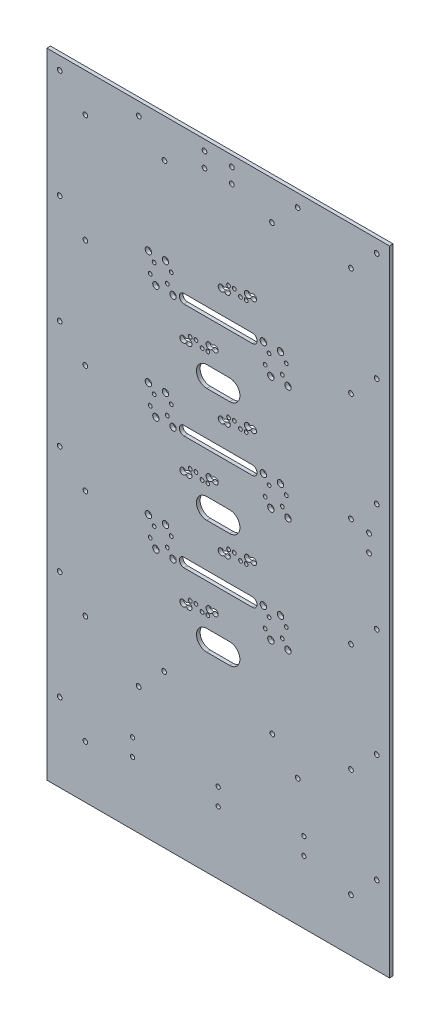
SolidWorks part; units mm, degrees
ref_plane "Front Plane" through (0, 0, 0) normal (0, 0, 1) x (1, 0, 0)
ref_plane "Top Plane" through (0, 0, 0) normal (0, 1, 0) x (1, 0, 0)
ref_plane "Right Plane" through (0, 0, 0) normal (1, 0, 0) x (0, 0, -1)
sketch "Sketch1" plane through (0, 0, 0) normal (0, 0, 1) x (1, 0, 0)
  line L0 (-165.9868, 389.7156) -> (134.0132, 389.7156) construction
  line L1 (-165.9868, 389.7156) -> (134.0132, 389.7156)
  line L2 (-165.9868, 389.7156) -> (-165.9868, -165.2844)
  line L3 (-165.9868, -165.2844) -> (134.0132, -165.2844)
  line L4 (134.0132, 389.7156) -> (134.0132, -165.2844)
  line L5 (89.0132, -165.2844) -> (134.0132, -165.2844) construction
  line L6 (134.0132, 389.7156) -> (134.0132, -165.2844) construction
  dimension "D2" = 300
extrude "Boss-Extrude1" add sketch "Sketch1" along normal blind 3.175
sketch "Sketch2" plane through (0, 0, 0) normal (0, 0, -1) x (-1, 0, 0)
  line L0 (15.9868, -165.2844) -> (15.9868, 389.7156) construction
  line L1 (165.9868, -165.2844) -> (-134.0132, -165.2844) construction
  line L2 (-134.0132, 389.7156) -> (165.9868, 389.7156) construction
  line L3 (0.9868, 59.7156) -> (30.9868, 59.7156) construction
  line L4 (0.9868, 159.7156) -> (30.9868, 159.7156) construction
  line L5 (0.9868, 259.7156) -> (30.9868, 259.7156) construction
  point P8 (15.9868, 59.7156)
  point P11 (15.9868, 159.7156)
  dimension "D1" = 30
  dimension "D2" = 30
  dimension "D3" = 100
  dimension "D4" = 100
  dimension "D5" = 130
sketch "Sketch4" plane through (0, 0, 3.175) normal (0, 0, 1) x (1, 0, 0)
  line L0 (-45.9868, 259.7156) -> (14.0132, 259.7156) construction
  line L1 (-45.9868, 263.7156) -> (14.0132, 263.7156)
  line L2 (-45.9868, 255.7156) -> (14.0132, 255.7156)
  line L3 (-15.9868, -165.2844) -> (-15.9868, 389.7156) construction
  line L4 (-0.9868, 259.7156) -> (-30.9868, 259.7156) construction
  line L5 (-45.9868, 159.7156) -> (14.0132, 159.7156) construction
  line L6 (-45.9868, 163.7156) -> (14.0132, 163.7156)
  line L7 (-45.9868, 155.7156) -> (14.0132, 155.7156)
  line L8 (-45.9868, 59.7156) -> (14.0132, 59.7156) construction
  line L9 (-45.9868, 63.7156) -> (14.0132, 63.7156)
  line L10 (-45.9868, 55.7156) -> (14.0132, 55.7156)
  line L11 (-0.9868, 59.7156) -> (-30.9868, 59.7156) construction
  line L12 (-0.9868, 159.7156) -> (-30.9868, 159.7156) construction
  arc A0 (-45.9868, 263.7156) -> (-45.9868, 255.7156) centre (-45.9868, 259.7156) ccw
  arc A1 (14.0132, 255.7156) -> (14.0132, 263.7156) centre (14.0132, 259.7156) ccw
  arc A2 (-45.9868, 163.7156) -> (-45.9868, 155.7156) centre (-45.9868, 159.7156) ccw
  arc A3 (14.0132, 155.7156) -> (14.0132, 163.7156) centre (14.0132, 159.7156) ccw
  arc A4 (-45.9868, 63.7156) -> (-45.9868, 55.7156) centre (-45.9868, 59.7156) ccw
  arc A5 (14.0132, 55.7156) -> (14.0132, 63.7156) centre (14.0132, 59.7156) ccw
  point P2 (-15.9868, 259.7156)
  point P14 (-15.9868, 159.7156)
  point P21 (-15.9868, 59.7156)
  dimension "D1" = 15
  dimension "D2" = 8
  dimension "D3" = 15
  dimension "D4" = 8
  dimension "D5" = 15
  dimension "D6" = 8
extrude "Cut-Extrude1" cut sketch "Sketch4" against normal blind 10
sketch "Sketch5" plane through (0, 0, 0) normal (0, 0, -1) x (-1, 0, 0)
  line L0 (45.9868, 155.7156) -> (-14.0132, 155.7156) construction
sketch "Sketch6" plane through (0, 0, 0) normal (0, 0, -1) x (-1, 0, 0)
  line L0 (-134.0132, 389.7156) -> (165.9868, 389.7156) construction
  circle A0 centre (3.9868, 380.7156) radius 2.05
  circle A1 centre (27.9868, 380.7156) radius 2.05
  circle A2 centre (27.9868, 367.7156) radius 2.05
  circle A3 centre (3.9868, 367.7156) radius 2.05
  point P12 (42.9868, 389.7156)
  point P13 (0, 0)
  point P16 (0, 0)
  point P17 (0, 0)
  point P18 (0, 0)
  point P21 (0, 0)
  dimension "D1" = 15
  dimension "D2" = 4.1
  dimension "D3" = 39
  dimension "D4" = 9
  dimension "D5" = 22
extrude "Cut-Extrude5" cut sketch "Sketch6" against normal blind 51
sketch "Sketch8" plane through (0, 0, 0) normal (0, 0, -1) x (-1, 0, 0)
  circle A0 centre (-116.0132, 162.9803) radius 2.1
  circle A1 centre (-116.0132, 147.9803) radius 2.1
  dimension "D1" = 4.2
extrude "Cut-Extrude7" cut sketch "Sketch8" against normal blind 67
sketch "Sketch9" plane through (0, 0, 0) normal (0, 0, -1) x (-1, 0, 0)
  line L0 (15.9868, 389.7156) -> (15.9868, 432.1874) construction
  line L1 (-134.0132, 389.7156) -> (165.9868, 389.7156) construction
  circle A0 centre (-122.7632, 378.4656) radius 2.05
  circle A1 centre (-100.2632, 355.9656) radius 2.05
  circle A2 centre (-53.5368, 378.4656) radius 2.05
  circle A3 centre (-31.0368, 355.9656) radius 2.05
  circle A4 centre (-122.7632, 283.4656) radius 2.05
  circle A5 centre (-100.2632, 260.9656) radius 2.05
  circle A6 centre (-122.7632, 188.4656) radius 2.05
  circle A7 centre (-100.2632, 165.9656) radius 2.05
  circle A8 centre (-122.7632, 93.4656) radius 2.05
  circle A9 centre (-100.2632, 70.9656) radius 2.05
  circle A10 centre (-122.7632, -1.5344) radius 2.05
  circle A11 centre (-100.2632, -24.0344) radius 2.05
  circle A12 centre (-122.7632, -96.5344) radius 2.05
  circle A13 centre (-100.2632, -119.0344) radius 2.05
  circle A14 centre (-122.7632, -191.5344) radius 2.05
  circle A15 centre (-100.2632, -214.0344) radius 2.05
  circle A16 centre (-53.6482, -54.0344) radius 2.05
  circle A17 centre (-31.371, -31.5344) radius 2.05
  circle A18 centre (63.3447, -31.5344) radius 2.05
  circle A19 centre (85.6219, -54.0344) radius 2.05
  circle A20 centre (132.2368, -214.0344) radius 2.05
  circle A21 centre (154.7368, -191.5344) radius 2.05
  circle A22 centre (132.2368, -119.0344) radius 2.05
  circle A23 centre (154.7368, -96.5344) radius 2.05
  circle A24 centre (132.2368, -24.0344) radius 2.05
  circle A25 centre (154.7368, -1.5344) radius 2.05
  circle A26 centre (132.2368, 70.9656) radius 2.05
  circle A27 centre (154.7368, 93.4656) radius 2.05
  circle A28 centre (132.2368, 165.9656) radius 2.05
  circle A29 centre (154.7368, 188.4656) radius 2.05
  circle A30 centre (132.2368, 260.9656) radius 2.05
  circle A31 centre (154.7368, 283.4656) radius 2.05
  circle A32 centre (63.0104, 355.9656) radius 2.05
  circle A33 centre (85.5104, 378.4656) radius 2.05
  circle A34 centre (132.2368, 355.9656) radius 2.05
  circle A35 centre (154.7368, 378.4656) radius 2.05
  dimension "D1" = 7
extrude "Cut-Extrude8" cut sketch "Sketch9" against normal blind 10
sketch "Sketch10" plane through (0, 0, 0) normal (0, 0, -1) x (-1, 0, 0)
  circle A0 centre (35.464, 33.6216) radius 1.651
  circle A1 centre (25.1051, 30.1602) radius 1.651
  arc A2 (43.5999, 30.6974) -> (43.5999, 26.4941) centre (41.7588, 28.5958) ccw
  arc A3 (20.6514, 37.2877) -> (20.6514, 33.0844) centre (18.8103, 35.186) ccw
  circle A4 centre (-30.1263, 38.9336) radius 2.794
  circle A5 centre (-23.5434, 61.8842) radius 2.794
  circle A6 centre (-25.1024, 45.23) radius 1.651
  circle A7 centre (-28.5672, 55.5878) radius 1.651
  circle A8 centre (-45.1263, 38.9336) radius 2.794
  circle A9 centre (-38.5434, 61.8842) radius 2.794
  circle A10 centre (-40.1024, 45.23) radius 1.651
  circle A11 centre (-43.5672, 55.5878) radius 1.651
  circle A12 centre (40.464, 33.6216) radius 1.651
  circle A13 centre (30.1051, 30.1602) radius 1.651
  arc A14 (44.9177, 26.4941) -> (44.9177, 30.6974) centre (46.7588, 28.5958) ccw
  arc A15 (21.9693, 33.0844) -> (21.9693, 37.2877) centre (23.8103, 35.186) ccw
  arc A16 (21.9693, 33.0844) -> (20.6514, 33.0844) centre (21.3103, 32.3322) ccw
  arc A17 (21.9693, 37.2877) -> (20.6514, 37.2877) centre (21.3103, 38.0399) cw
  arc A18 (44.9177, 26.4941) -> (43.5999, 26.4941) centre (44.2588, 25.7419) ccw
  arc A19 (44.9177, 30.6974) -> (43.5999, 30.6974) centre (44.2588, 31.4496) cw
  circle A40 centre (55.5171, 57.5469) radius 2.794
  circle A41 centre (70.5171, 57.5469) radius 2.794
  circle A42 centre (75.5409, 63.8433) radius 1.651
  circle A43 centre (60.5409, 63.8433) radius 1.651
  circle A44 centre (-3.4904, 85.8095) radius 1.651
  circle A45 centre (6.8686, 89.271) radius 1.651
  arc A46 (-11.6262, 88.7337) -> (-11.6262, 92.937) centre (-9.7851, 90.8353) ccw
  arc A47 (11.3223, 82.1435) -> (11.3223, 86.3468) centre (13.1633, 84.2451) ccw
  circle A48 centre (62.0999, 80.4975) radius 2.794
  circle A49 centre (57.0761, 74.2011) radius 1.651
  circle A50 centre (77.0999, 80.4975) radius 2.794
  circle A51 centre (72.0761, 74.2011) radius 1.651
  circle A52 centre (-8.4904, 85.8095) radius 1.651
  circle A53 centre (1.8686, 89.271) radius 1.651
  arc A54 (-12.9441, 92.937) -> (-12.9441, 88.7337) centre (-14.7851, 90.8353) ccw
  arc A55 (10.0044, 86.3468) -> (10.0044, 82.1435) centre (8.1633, 84.2451) ccw
  arc A56 (10.0044, 86.3468) -> (11.3223, 86.3468) centre (10.6633, 87.099) ccw
  arc A57 (10.0044, 82.1435) -> (11.3223, 82.1435) centre (10.6633, 81.3913) cw
  arc A58 (-12.9441, 92.937) -> (-11.6262, 92.937) centre (-12.2851, 93.6892) ccw
  arc A59 (-12.9441, 88.7337) -> (-11.6262, 88.7337) centre (-12.2851, 87.9815) cw
  circle A60 centre (63.0104, 355.9656) radius 2.05 construction
  circle A62 centre (35.464, 133.6216) radius 1.651
  circle A63 centre (25.1051, 130.1602) radius 1.651
  arc A64 (43.5999, 130.6974) -> (43.5999, 126.4941) centre (41.7588, 128.5958) ccw
  arc A65 (20.6514, 137.2877) -> (20.6514, 133.0844) centre (18.8103, 135.186) ccw
  circle A66 centre (-30.1263, 138.9336) radius 2.794
  circle A67 centre (-23.5434, 161.8842) radius 2.794
  circle A68 centre (-25.1024, 145.23) radius 1.651
  circle A69 centre (-28.5672, 155.5878) radius 1.651
  circle A70 centre (-45.1263, 138.9336) radius 2.794
  circle A71 centre (-38.5434, 161.8842) radius 2.794
  circle A72 centre (-40.1024, 145.23) radius 1.651
  circle A73 centre (-43.5672, 155.5878) radius 1.651
  circle A74 centre (40.464, 133.6216) radius 1.651
  circle A75 centre (30.1051, 130.1602) radius 1.651
  arc A76 (44.9177, 126.4941) -> (44.9177, 130.6974) centre (46.7588, 128.5958) ccw
  arc A77 (21.9693, 133.0844) -> (21.9693, 137.2877) centre (23.8103, 135.186) ccw
  arc A78 (21.9693, 133.0844) -> (20.6514, 133.0844) centre (21.3103, 132.3322) ccw
  arc A79 (21.9693, 137.2877) -> (20.6514, 137.2877) centre (21.3103, 138.0399) cw
  arc A80 (44.9177, 126.4941) -> (43.5999, 126.4941) centre (44.2588, 125.7419) ccw
  arc A81 (44.9177, 130.6974) -> (43.5999, 130.6974) centre (44.2588, 131.4496) cw
  circle A82 centre (55.5171, 157.5469) radius 2.794
  circle A83 centre (70.5171, 157.5469) radius 2.794
  circle A84 centre (75.5409, 163.8433) radius 1.651
  circle A85 centre (60.5409, 163.8433) radius 1.651
  circle A86 centre (-3.4904, 185.8095) radius 1.651
  circle A87 centre (6.8686, 189.271) radius 1.651
  arc A88 (-11.6262, 188.7337) -> (-11.6262, 192.937) centre (-9.7851, 190.8353) ccw
  arc A89 (11.3223, 182.1435) -> (11.3223, 186.3468) centre (13.1633, 184.2451) ccw
  circle A90 centre (62.0999, 180.4975) radius 2.794
  circle A91 centre (57.0761, 174.2011) radius 1.651
  circle A92 centre (77.0999, 180.4975) radius 2.794
  circle A93 centre (72.0761, 174.2011) radius 1.651
  circle A94 centre (-8.4904, 185.8095) radius 1.651
  circle A95 centre (1.8686, 189.271) radius 1.651
  arc A96 (-12.9441, 192.937) -> (-12.9441, 188.7337) centre (-14.7851, 190.8353) ccw
  arc A97 (10.0044, 186.3468) -> (10.0044, 182.1435) centre (8.1633, 184.2451) ccw
  arc A98 (10.0044, 186.3468) -> (11.3223, 186.3468) centre (10.6633, 187.099) ccw
  arc A99 (10.0044, 182.1435) -> (11.3223, 182.1435) centre (10.6633, 181.3913) cw
  arc A100 (-12.9441, 192.937) -> (-11.6262, 192.937) centre (-12.2851, 193.6892) ccw
  arc A101 (-12.9441, 188.7337) -> (-11.6262, 188.7337) centre (-12.2851, 187.9815) cw
  circle A102 centre (35.464, 233.6216) radius 1.651
  circle A103 centre (25.1051, 230.1602) radius 1.651
  arc A104 (43.5999, 230.6974) -> (43.5999, 226.4941) centre (41.7588, 228.5958) ccw
  arc A105 (20.6514, 237.2877) -> (20.6514, 233.0844) centre (18.8103, 235.186) ccw
  circle A106 centre (-30.1263, 238.9336) radius 2.794
  circle A107 centre (-23.5434, 261.8842) radius 2.794
  circle A108 centre (-25.1024, 245.23) radius 1.651
  circle A109 centre (-28.5672, 255.5878) radius 1.651
  circle A110 centre (-45.1263, 238.9336) radius 2.794
  circle A111 centre (-38.5434, 261.8842) radius 2.794
  circle A112 centre (-40.1024, 245.23) radius 1.651
  circle A113 centre (-43.5672, 255.5878) radius 1.651
  circle A114 centre (40.464, 233.6216) radius 1.651
  circle A115 centre (30.1051, 230.1602) radius 1.651
  arc A116 (44.9177, 226.4941) -> (44.9177, 230.6974) centre (46.7588, 228.5958) ccw
  arc A117 (21.9693, 233.0844) -> (21.9693, 237.2877) centre (23.8103, 235.186) ccw
  arc A118 (21.9693, 233.0844) -> (20.6514, 233.0844) centre (21.3103, 232.3322) ccw
  arc A119 (21.9693, 237.2877) -> (20.6514, 237.2877) centre (21.3103, 238.0399) cw
  arc A120 (44.9177, 226.4941) -> (43.5999, 226.4941) centre (44.2588, 225.7419) ccw
  arc A121 (44.9177, 230.6974) -> (43.5999, 230.6974) centre (44.2588, 231.4496) cw
  circle A122 centre (55.5171, 257.5469) radius 2.794
  circle A123 centre (70.5171, 257.5469) radius 2.794
  circle A124 centre (75.5409, 263.8433) radius 1.651
  circle A125 centre (60.5409, 263.8433) radius 1.651
  circle A126 centre (-3.4904, 285.8095) radius 1.651
  circle A127 centre (6.8686, 289.271) radius 1.651
  arc A128 (-11.6262, 288.7337) -> (-11.6262, 292.937) centre (-9.7851, 290.8353) ccw
  arc A129 (11.3223, 282.1435) -> (11.3223, 286.3468) centre (13.1633, 284.2451) ccw
  circle A130 centre (62.0999, 280.4975) radius 2.794
  circle A131 centre (57.0761, 274.2011) radius 1.651
  circle A132 centre (77.0999, 280.4975) radius 2.794
  circle A133 centre (72.0761, 274.2011) radius 1.651
  circle A134 centre (-8.4904, 285.8095) radius 1.651
  circle A135 centre (1.8686, 289.271) radius 1.651
  arc A136 (-12.9441, 292.937) -> (-12.9441, 288.7337) centre (-14.7851, 290.8353) ccw
  arc A137 (10.0044, 286.3468) -> (10.0044, 282.1435) centre (8.1633, 284.2451) ccw
  arc A138 (10.0044, 286.3468) -> (11.3223, 286.3468) centre (10.6633, 287.099) ccw
  arc A139 (10.0044, 282.1435) -> (11.3223, 282.1435) centre (10.6633, 281.3913) cw
  arc A140 (-12.9441, 292.937) -> (-11.6262, 292.937) centre (-12.2851, 293.6892) ccw
  arc A141 (-12.9441, 288.7337) -> (-11.6262, 288.7337) centre (-12.2851, 287.9815) cw
  dimension "D3" = 1
  dimension "D4" = 1
  dimension "D5" = 3
  dimension "D1" = 2
  dimension "D2" = 2
extrude "Cut-Extrude9" cut sketch "Sketch10" against normal blind 10
sketch "Sketch12" plane through (0, 0, 0) normal (0, 0, -1) x (-1, 0, 0)
  circle A0 centre (90.9868, -95.2078) radius 1.85
  circle A1 centre (90.9868, -110.2078) radius 1.85
  circle A2 centre (15.9868, -95.2078) radius 1.85
  circle A3 centre (15.9868, -110.2078) radius 1.85
  circle A4 centre (-59.0132, -95.2078) radius 1.85
  circle A5 centre (-59.0132, -110.2078) radius 1.85
  dimension "D1" = 3
extrude "Cut-Extrude10" cut sketch "Sketch12" against normal blind 10
sketch "Sketch13" plane through (0, 0, 3.175) normal (0, 0, 1) x (1, 0, 0)
  line L0 (-15.9868, 55.7156) -> (-15.9868, 10.7156) construction
  line L1 (-45.9868, 55.7156) -> (14.0132, 55.7156) construction
  line L2 (-25.9868, 10.7156) -> (-5.9868, 10.7156) construction
  line L3 (-25.9868, 19.7156) -> (-5.9868, 19.7156)
  line L4 (-25.9868, 1.7156) -> (-5.9868, 1.7156)
  line L5 (14.0132, 63.7156) -> (-45.9868, 63.7156) construction
  line L6 (14.0132, 163.7156) -> (-45.9868, 163.7156) construction
  line L7 (-25.9868, 110.7156) -> (-5.9868, 110.7156) construction
  line L8 (-25.9868, 119.7156) -> (-5.9868, 119.7156)
  line L9 (-25.9868, 101.7156) -> (-5.9868, 101.7156)
  line L10 (-25.9868, 210.7156) -> (-5.9868, 210.7156) construction
  line L11 (-25.9868, 219.7156) -> (-5.9868, 219.7156)
  line L12 (-25.9868, 201.7156) -> (-5.9868, 201.7156)
  arc A0 (-25.9868, 19.7156) -> (-25.9868, 1.7156) centre (-25.9868, 10.7156) ccw
  arc A1 (-5.9868, 1.7156) -> (-5.9868, 19.7156) centre (-5.9868, 10.7156) ccw
  arc A2 (-25.9868, 119.7156) -> (-25.9868, 101.7156) centre (-25.9868, 110.7156) ccw
  arc A3 (-5.9868, 101.7156) -> (-5.9868, 119.7156) centre (-5.9868, 110.7156) ccw
  arc A4 (-25.9868, 219.7156) -> (-25.9868, 201.7156) centre (-25.9868, 210.7156) ccw
  arc A5 (-5.9868, 201.7156) -> (-5.9868, 219.7156) centre (-5.9868, 210.7156) ccw
  point P6 (-15.9868, 10.7156)
  point P19 (-15.9868, 110.7156)
  point P26 (-15.9868, 210.7156)
  dimension "D1" = 18
  dimension "D2" = 45
  dimension "D3" = 20
  dimension "D4" = 100
  dimension "D6" = 100
  dimension "D5" = 3
extrude "Cut-Extrude11" cut sketch "Sketch13" against normal blind 29.1
